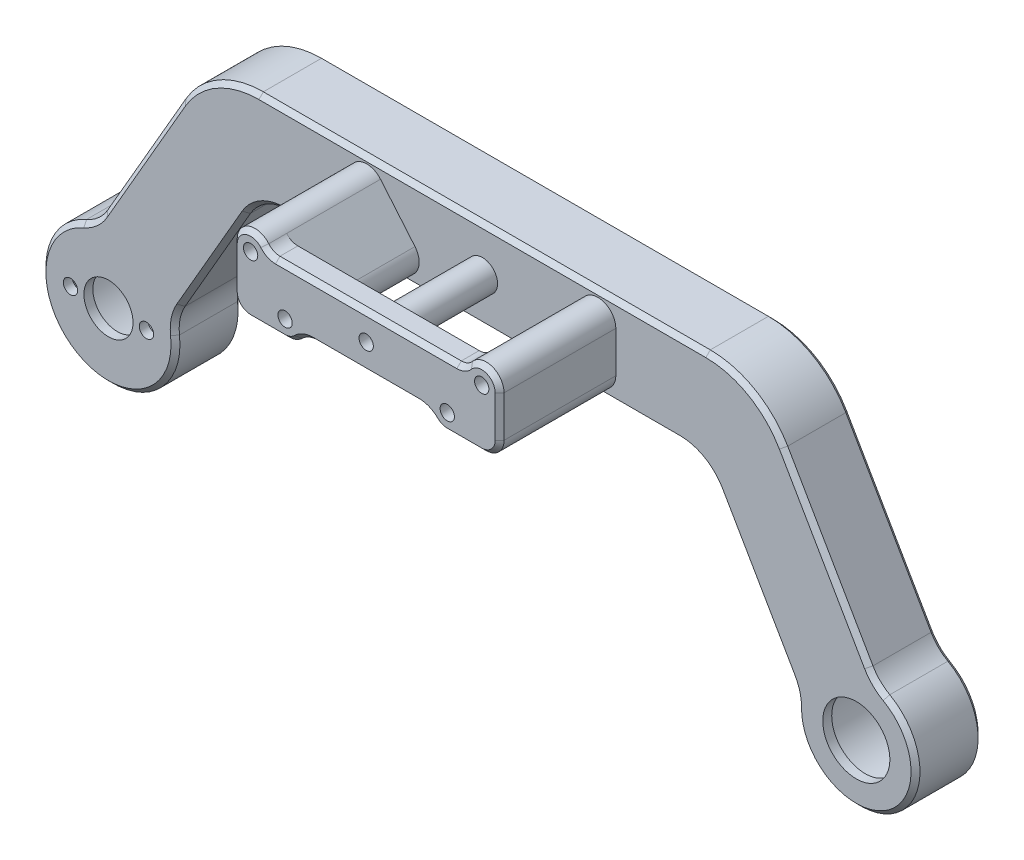
SolidWorks part; units mm, degrees
other "Markup1"
sketch "Sketch2"
ref_plane "Front Plane" through (0, 0, 0) normal (0, 0, 1) x (1, 0, 0)
ref_plane "Top Plane" through (0, 0, 0) normal (0, 1, 0) x (1, 0, 0)
ref_plane "Right Plane" through (0, 0, 0) normal (1, 0, 0) x (0, 0, -1)
ref_axis "X" through (-88.99, 0, 0) along (1, 0, 0)
ref_axis "Y" through (0, 55, 0) along (0, -1, 0)
ref_axis "Z" through (0, 0, -88.99) along (0, 0, 1)
sketch "Sketch1" plane through (0, 0, 0) normal (0, 0, 1) x (1, 0, 0)
  line L0 (0, 10) -> (0, -10) construction
  line L1 (-50, 10) -> (50, 10)
  line L2 (-50, -10) -> (50, -10)
  line L3 (67.3205, 0) -> (92.3205, -43.3013)
  line L4 (75, -53.3013) -> (50, -10)
  line L5 (-75, -53.3013) -> (-50, -10)
  line L6 (-67.3205, 0) -> (-92.3205, -43.3013)
  arc A0 (50, 10) -> (67.3205, 0) centre (50, -10) cw
  arc A1 (92.3205, -43.3013) -> (75, -53.3013) centre (83.6603, -48.3013) cw
  arc A3 (-92.3205, -43.3013) -> (-75, -53.3013) centre (-83.6603, -48.3013) ccw
  arc A4 (-50, 10) -> (-67.3205, 0) centre (-50, -10) ccw
  point P4 (0, 0)
  dimension "D1" = 20
  dimension "D2" = 50
  dimension "D3" = 60
  dimension "D4" = 50
extrude "Boss-Extrude1" add sketch "Sketch1" along normal mid plane 15
ref_plane "Plane1" through (0, 0, 28.5) normal (0, 0, 1) x (1, 0, 0)
sketch "Sketch3" plane through (0, 0, 0) normal (0, 0, 1) x (1, 0, 0)
  line L0 (-22, 0) -> (22, 0) construction
  line L1 (25.8567, 4.5963) -> (18.1433, -4.5963) construction
  line L2 (0, 0) -> (0, 1.6) construction
  line L3 (-25.8567, 4.5963) -> (-18.1433, -4.5963) construction
  circle A1 centre (0, 0) radius 1.6
  circle A2 centre (25.8567, 4.5963) radius 1.6
  circle A3 centre (18.1433, -4.5963) radius 1.6
  circle A4 centre (-25.8567, 4.5963) radius 1.6
  circle A5 centre (-18.1433, -4.5963) radius 1.6
  point P7 (0, 0)
  point P10 (22, 0)
  dimension "D6" = 3.2
  dimension "D3" = 12
  dimension "D4" = 22
  dimension "D5" = 50
extrude "Cut-Extrude1" cut sketch "Sketch3" against normal through all both and the other way through all
sketch "Sketch4" plane through (0, 0, 28.5) normal (0, 0, 1) x (1, 0, 0)
  line L0 (25.8567, 4.5963) -> (18.1433, -4.5963) construction
  line L1 (-25.8567, 4.5963) -> (-18.1433, -4.5963) construction
  line L2 (25.8567, 4.5963) -> (18.1433, -4.5963) construction
  line L3 (-25.8567, 4.5963) -> (-18.1433, -4.5963) construction
  line L4 (15.0791, -2.0251) -> (22.7925, 7.1674)
  line L5 (29.8567, 4.5963) -> (29.8567, -4.5963)
  line L6 (25.8567, -8.5963) -> (18.1433, -8.5963)
  line L7 (0, 0) -> (0, 1.6) construction
  line L8 (0, 0) -> (0, 1.6) construction
  line L9 (-25.8567, -8.5963) -> (-18.1433, -8.5963)
  line L10 (-29.8567, 4.5963) -> (-29.8567, -4.5963)
  line L11 (-15.0791, -2.0251) -> (-22.7925, 7.1674)
  line L12 (20.289, 6) -> (-20.289, 6)
  line L13 (0, 6) -> (0, 3.4)
  line L14 (0, -3.4) -> (0, -6)
  line L15 (-11.8193, -6) -> (11.8193, -6)
  circle A0 centre (25.8567, 4.5963) radius 1.6 construction
  circle A1 centre (18.1433, -4.5963) radius 1.6 construction
  circle A2 centre (-25.8567, 4.5963) radius 1.6 construction
  circle A3 centre (-18.1433, -4.5963) radius 1.6 construction
  circle A4 centre (0, 0) radius 1.6 construction
  circle A5 centre (25.8567, 4.5963) radius 1.6
  circle A6 centre (18.1433, -4.5963) radius 1.6
  circle A7 centre (-25.8567, 4.5963) radius 1.6
  circle A8 centre (-18.1433, -4.5963) radius 1.6
  circle A9 centre (0, 0) radius 1.6
  arc A10 (22.7925, 7.1674) -> (29.8567, 4.5963) centre (25.8567, 4.5963) cw
  arc A11 (29.8567, -4.5963) -> (25.8567, -8.5963) centre (25.8567, -4.5963) cw
  arc A12 (18.1433, -8.5963) -> (15.0791, -2.0251) centre (18.1433, -4.5963) cw
  arc A13 (-29.8567, -4.5963) -> (-25.8567, -8.5963) centre (-25.8567, -4.5963) ccw
  arc A14 (-22.7925, 7.1674) -> (-29.8567, 4.5963) centre (-25.8567, 4.5963) ccw
  arc A15 (-18.1433, -8.5963) -> (-15.0791, -2.0251) centre (-18.1433, -4.5963) ccw
  circle A16 centre (0, 0) radius 3.4
  arc A17 (22.7925, 7.1674) -> (20.289, 6) centre (20.289, 9.2681) cw
  arc A18 (11.8193, -6) -> (15.3326, -7.4424) centre (11.8193, -11) cw
  arc A19 (-11.8193, -6) -> (-15.3326, -7.4424) centre (-11.8193, -11) ccw
  arc A20 (-22.7925, 7.1674) -> (-20.289, 6) centre (-20.289, 9.2681) ccw
  point P50 (12.7365, -8.5606)
  dimension "D1" = 4
  dimension "D4" = 4
  dimension "D5" = 6.8
  dimension "D6" = 12
  dimension "D7" = 5
  dimension "D2" = 4
  dimension "D3" = 4
extrude "Boss-Extrude2" add sketch "Sketch4" against normal up to surface (21 mm away) separate body contours L9 A15 L11 A14 L10 A13 A8 A7 | A12 L6 A11 L5 A10 L4 A6 A5 | A16 A9 region at (23.3022, -1.3358, 28.5) region at (2.3362, 2.3362, 28.5) region at (-23.3022, -1.3358, 28.5) up to face at (-19.7433, -4.5963, 7.5)
extrude "Boss-Extrude3" add sketch "Sketch4<3>" along normal blind 5 contours L9 A15 L11 A14 L10 A13 A8 A7 | A20 L11 A15 A19 L15 L14 A16 L13 L12 | A16 A9 | L15 A18 A12 L4 A17 L12 L13 A16 L14 | A12 L6 A11 L5 A10 L4 A6 A5 region at (9.4772, 0.5266, 28.5) region at (23.3022, -1.3358, 28.5) region at (-9.4772, 0.5266, 28.5) region at (2.3362, 2.3362, 28.5) region at (-23.3022, -1.3358, 28.5)
sketch "Sketch4<3>" plane through (0, 0, 28.5) normal (0, 0, 1) x (1, 0, 0) same geometry as "Sketch4"
chamfer "Chamfer1" distance 1 angle 45 16 edges at (22, -8.5963, 33.5) (28.6852, -7.4247, 33.5) (16.6241, -8.2966, 33.5) (29.8567, 0, 33.5) (13.7183, -6.3746, 33.5) (27.2248, 8.355, 33.5) (0, -6, 33.5) (21.6702, 6.3062, 33.5) (-13.7183, -6.3746, 33.5) (0, 6, 33.5) (-16.6241, -8.2966, 33.5) (-21.6702, 6.3062, 33.5) (-22, -8.5963, 33.5) (-27.2248, 8.355, 33.5) (-28.6852, -7.4247, 33.5) (-29.8567, 0, 33.5)
sketch "Sketch5" plane through (0, 0, 0) normal (0, 0, 1) x (1, 0, 0)
  line L0 (-92.1603, -48.3013) -> (-75.1603, -48.3013) construction
  circle A1 centre (83.6603, -48.3013) radius 13.25
  circle A3 centre (83.6603, -48.3013) radius 11.25
  circle A4 centre (83.6603, -48.3013) radius 7.5
  circle A5 centre (-83.6603, -48.3013) radius 13
  circle A6 centre (-83.6603, -48.3013) radius 15
  circle A7 centre (-83.6603, -48.3013) radius 5.5
  circle A8 centre (-75.1603, -48.3013) radius 1.6
  circle A9 centre (-92.1603, -48.3013) radius 1.6
  point P14 (-83.6603, -48.3013)
  dimension "D1" = 2
  dimension "D2" = 22.5
  dimension "D3" = 15
  dimension "D4" = 26
  dimension "D6" = 11
  dimension "D8" = 3.2
  dimension "D7" = 17
  dimension "D5" = 2
extrude "Boss-Extrude4" add sketch "Sketch5" along normal up to surface and the other way up to surface contours A1 A3 region at (70.785, -48.3013, 0) up to face at (-19.7433, -4.5963, 7.5) other way up to face at (-19.7433, -4.5963, -7.5)
extrude "Cut-Extrude2" cut sketch "Sketch5<3>" against normal through all both and the other way through all contours A3
sketch "Sketch5<3>" plane through (0, 0, 0) normal (0, 0, 1) x (1, 0, 0) same geometry as "Sketch5"
extrude "Boss-Extrude5" add sketch "Sketch5<4>" against normal blind 2 from surface contours A3 A4 region at (72.7285, -48.3013, 0) starting at face at (72.4103, -48.3013, 7.5)
sketch "Sketch5<4>" plane through (0, 0, 0) normal (0, 0, 1) x (1, 0, 0) same geometry as "Sketch5"
extrude "Cut-Extrude3" cut sketch "Sketch5<5>" against normal through all both and the other way through all contours A5
sketch "Sketch5<5>" plane through (0, 0, 0) normal (0, 0, 1) x (1, 0, 0) same geometry as "Sketch5"
extrude "Boss-Extrude6" add sketch "Sketch5<6>" along normal up to surface (7.5 mm away) and the other way up to surface (7.5 mm away) contours A6 A5 region at (-98.236, -48.3013, 0) up to face at (1.2932, -17.4059, 7.5) other way up to face at (1.2932, -17.4059, -7.5)
sketch "Sketch5<6>" plane through (0, 0, 0) normal (0, 0, 1) x (1, 0, 0) same geometry as "Sketch5"
extrude "Boss-Extrude7" add sketch "Sketch5<7>" against normal blind 2 from surface contours A5 A9 A7 A8 region at (-96.2926, -48.3013, 0) starting at face at (0.0369, -19.5819, 7.5)
sketch "Sketch5<7>" plane through (0, 0, 0) normal (0, 0, 1) x (1, 0, 0) same geometry as "Sketch5"
fillet "Fillet1" radius 10 6 edges at (87.9742, -35.7732, 0) (70.6537, -45.7732, 0) (-86.7303, -33.6188, 0) (-69.4098, -43.6188, 0) (50, -10, 0) (-50, -10, 0)
chamfer "Chamfer2" distance 1 angle 45 32 edges at (0, -10, -7.5) (49.2265, -11.3397, -7.5) (-49.2265, -11.3397, -7.5) (60.9794, -29.0169, -7.5) (-60.1934, -27.6554, -7.5) (70.0858, -45.5012, -7.5) (-68.6367, -43.3061, -7.5) (90.2853, -59.7761, -7.5) (-91.1603, -61.2917, -7.5) (88.0225, -35.1454, -7.5) (-86.8461, -32.7929, -7.5) (76.8565, -16.5169, -7.5) (-76.0705, -15.1554, -7.5) (60, 7.3205, -7.5) (-60, 7.3205, -7.5) (0, 10, -7.5) (0, -10, 7.5) (49.2265, -11.3397, 7.5) (-49.2265, -11.3397, 7.5) (60.9794, -29.0169, 7.5) (-60.1934, -27.6554, 7.5) (70.0858, -45.5012, 7.5) (-68.6367, -43.3061, 7.5) (90.2853, -59.7761, 7.5) (-91.1603, -61.2917, 7.5) (88.0225, -35.1454, 7.5) (-86.8461, -32.7929, 7.5) (76.8565, -16.5169, 7.5) (-76.0705, -15.1554, 7.5) (60, 7.3205, 7.5) (-60, 7.3205, 7.5) (0, 10, 7.5)
